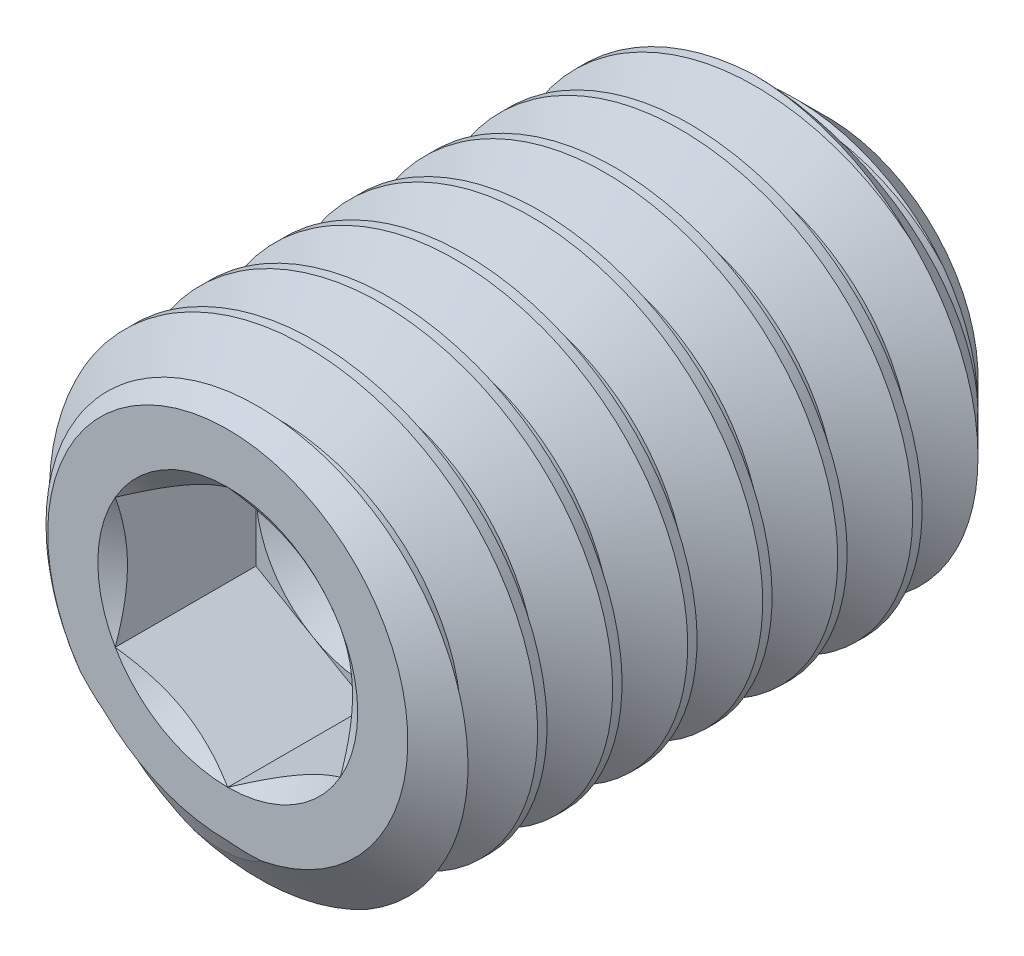
SolidWorks part; units mm, degrees
ref_plane "Front" through (0, 0, 0) normal (0, 0, 1) x (1, 0, 0)
ref_plane "Top" through (0, 0, 0) normal (0, 1, 0) x (1, 0, 0)
ref_plane "Right" through (0, 0, 0) normal (1, 0, 0) x (0, 0, -1)
sketch "Body Sketch" plane through (0, 0, 0) normal (1, 0, 0) x (0, 0, -1)
  line L0 (-2, 0) -> (-2, 1.2)
  line L1 (-2, 1.2) -> (-1.7899, 1.5)
  line L2 (-1.7899, 1.5) -> (1.5, 1.5)
  line L3 (1.5, 1.5) -> (2, 1)
  line L4 (-0.145, 1.5) -> (-0.145, -1.5) construction
  line L5 (2, 0) -> (-2, 0)
  line L6 (-2, 1.2) -> (-2, -1.2) construction
  line L7 (2, 0) -> (2, 1)
  point P11 (-0.145, 0)
  dimension "Length" = 4
  dimension "D3" = 35
  dimension "D6" = 45
  dimension "Dia" = 3
  dimension "D1" = 2.4
  dimension "D2" = 0.5
revolve "Body Revolve" add sketch "Body Sketch" angle 360 about L5
ref_plane "Plane1" through (0, 0, -2) normal (0, 0, 1) x (1, 0, 0)
sketch "Sketch27" plane through (0, 0, -2) normal (0, 0, 1) x (1, 0, 0)
  circle A0 centre (0, 0) radius 1.5 construction
  circle A1 centre (0, 0) radius 1.5
curve "Helix/Spiral1" pitch 0.5 height 4.5 radius 1.5 centre (0, 0, -2) axis (0, 0, 1) start towards (0, 1, 0)
sketch "Sketch28" plane through (0, 0, 0) normal (1, 0, 0) x (0, 0, -1)
  line L0 (2, 1.5) -> (2.4375, 1.5)
  line L1 (2.4375, 1.5) -> (2.25, 1.1752)
  line L2 (2.25, 1.1752) -> (2.1875, 1.1752)
  line L3 (2.1875, 1.1752) -> (2, 1.5)
  line L4 (2.0937, 1.3376) -> (2.3437, 1.3376) construction
  line L6 (-1.7899, 1.5) -> (1.5, 1.5) construction
  dimension "D1" = 0.0625
  dimension "D3" = 60
  dimension "D2" = 0.25
sweep "Cut-Sweep2" cut profiles "Sketch28" path "Helix/Spiral1" align with end faces yes
sketch "Sketch23" plane through (0, 0, 2) normal (0, 0, 1) x (1, 0, 0)
  line L1 (0, 0.866) -> (-0.75, 0.433)
  line L2 (-0.75, 0.433) -> (-0.75, -0.433)
  line L3 (-0.75, -0.433) -> (0, -0.866)
  line L4 (0, -0.866) -> (0.75, -0.433)
  line L5 (0.75, -0.433) -> (0.75, 0.433)
  line L6 (0.75, 0.433) -> (0, 0.866)
  circle A0 centre (0, 0) radius 0.75 construction
  dimension "Hex" = 1.5
extrude "Cut-Extrude10" cut sketch "Sketch23" against normal blind 0.9375
sketch "Sketch24" plane through (0, 0, 2) normal (0, 0, 1) x (1, 0, 0)
  circle A0 centre (0, 0) radius 0.866
extrude "Cut-Extrude11" cut sketch "Sketch24" against normal through all draft 55
sketch "Sketch26" plane through (0, 0, 1.0625) normal (0, 0, 1) x (1, 0, 0)
  circle A0 centre (0, 0) radius 0.75 construction
  circle A1 centre (0, 0) radius 0.75
extrude "Cut-Extrude12" cut sketch "Sketch26" against normal through all draft 60
equation "\"D1@Sketch28\" = \"D4@Helix/Spiral1\" * .125"
equation "\"D2@Sketch28\" = \"D4@Helix/Spiral1\" * .5"
equation "\"D3@Helix/Spiral1\" = \"Length@Body Sketch\" + \"D4@Helix/Spiral1\""
equation "\"hex Depth@Cut-Extrude10\" = \"Hex@Sketch23\" * .625"
equation "\"D1@Body Sketch\" = \"Dia@Body Sketch\" * .8"
equation "\"D2@Body Sketch\" = \"D4@Helix/Spiral1\""
